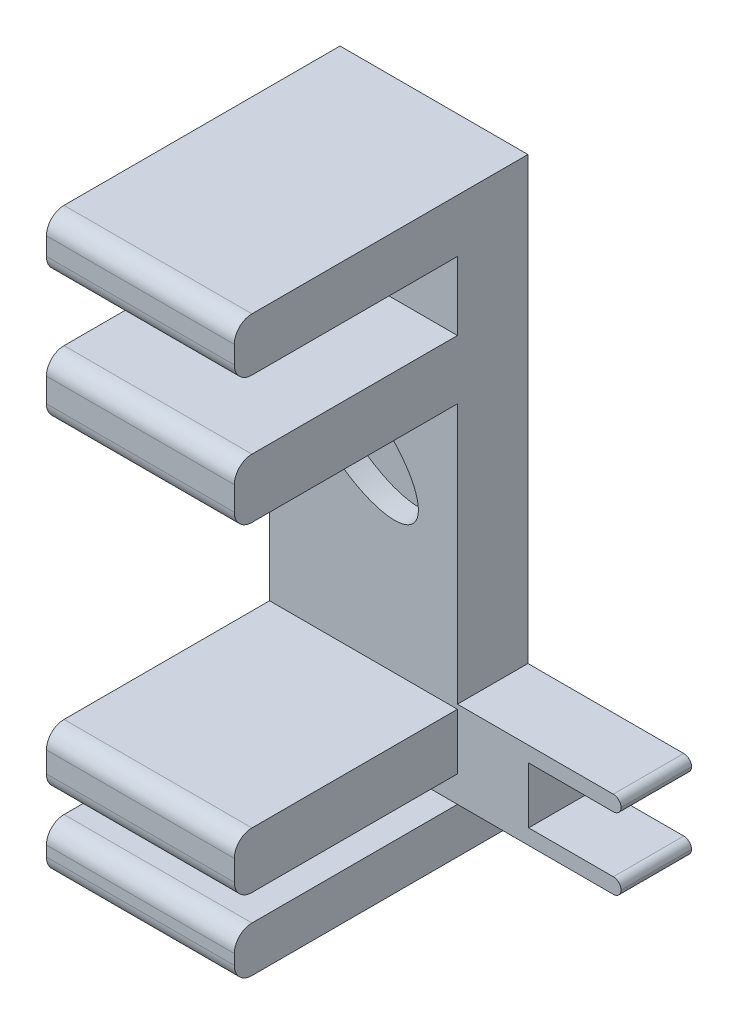
SolidWorks part; units mm, degrees
ref_plane "Front Plane" through (0, 0, 0) normal (0, 0, 1) x (1, 0, 0)
ref_plane "Top Plane" through (0, 0, 0) normal (0, 1, 0) x (1, 0, 0)
ref_plane "Right Plane" through (0, 0, 0) normal (1, 0, 0) x (0, 0, -1)
sketch "Sketch2" plane through (0, 0, 0) normal (0, 0, 1) x (1, 0, 0)
  line L0 (80, 56.32) -> (149.68, 56.32)
  line L1 (0, 0) -> (80, 0)
  line L2 (0, 0) -> (0, 244)
  line L3 (0, 244) -> (80, 244)
  line L4 (80, 0) -> (80, 56.32)
  line L5 (149.68, 56.32) -> (149.68, 49.83)
  line L6 (149.68, 49.83) -> (110.31, 49.83)
  line L7 (110.31, 49.83) -> (110.31, 25.8796)
  line L8 (110.31, 25.8796) -> (149.68, 25.8796)
  line L9 (149.68, 25.8796) -> (149.68, 19.3896)
  line L10 (149.68, 19.3896) -> (80, 19.3896)
  line L11 (80, 244) -> (80, 56.32)
  dimension "D1" = 244
  dimension "D2" = 80
  dimension "D3" = 187.68
  dimension "D4" = 69.68
  dimension "D6" = 6.49
  dimension "D7" = 6.49
  dimension "D8" = 39.37
extrude "Boss-Extrude2" add sketch "Sketch2" along normal mid plane 30 contours L11 L3 L2 L1 L4 | L10 L9 L8 L7 L6 L5 L0 L4 region at (106.0751, 37.8548, 0) region at (40, 122, 0)
fillet "Fillet1" radius 3.33 4 edges at (149.68, 19.3896, 0) (149.68, 25.8796, 0) (149.68, 49.83, 0) (149.68, 56.32, 0)
sketch "Sketch3" plane through (0, 0, 0) normal (0, 0, 1) x (1, 0, 0)
  line L0 (0, 244) -> (80, 244) construction
  line L1 (0, 221.4078) -> (80, 221.4078)
  line L2 (0, 0) -> (0, 244) construction
  line L3 (80, 244) -> (80, 56.32) construction
  line L4 (80, 221.4078) -> (0, 221.4078)
  line L5 (80, 221.4078) -> (80, 244)
  line L6 (80, 244) -> (0, 244)
  line L7 (0, 221.4078) -> (0, 244)
  line L13 (80, 19.3896) -> (146.35, 19.3896)
  line L14 (146.35, 25.8796) -> (110.31, 25.8796)
  line L15 (110.31, 25.8796) -> (110.31, 49.83)
  line L16 (110.31, 49.83) -> (146.35, 49.83)
  line L17 (146.35, 56.32) -> (80, 56.32)
  line L18 (80, 56.32) -> (80, 244)
  line L19 (80, 244) -> (0, 244)
  line L20 (0, 244) -> (0, 0)
  line L21 (0, 0) -> (80, 0)
  line L22 (80, 0) -> (80, 19.3896)
  line L23 (80, 19.3896) -> (146.35, 19.3896)
  line L24 (146.35, 25.8796) -> (110.31, 25.8796)
  line L25 (110.31, 25.8796) -> (110.31, 49.83)
  line L26 (110.31, 49.83) -> (146.35, 49.83)
  line L27 (146.35, 56.32) -> (80, 56.32)
  line L28 (80, 56.32) -> (80, 221.4078)
  line L30 (0, 221.4078) -> (0, 0)
  line L31 (0, 0) -> (80, 0)
  line L32 (80, 0) -> (80, 19.3896)
  arc A4 (146.35, 19.3896) -> (149.6789, 22.6346) centre (146.35, 22.7196) ccw
  arc A5 (149.6789, 22.6346) -> (146.35, 25.8796) centre (146.35, 22.5496) ccw
  arc A6 (146.35, 49.83) -> (149.6789, 53.075) centre (146.35, 53.16) ccw
  arc A7 (149.6789, 53.075) -> (146.35, 56.32) centre (146.35, 52.99) ccw
  arc A8 (146.35, 19.3896) -> (149.6789, 22.6346) centre (146.35, 22.7196) ccw
  arc A9 (149.6789, 22.6346) -> (146.35, 25.8796) centre (146.35, 22.5496) ccw
  arc A10 (146.35, 49.83) -> (149.6789, 53.075) centre (146.35, 53.16) ccw
  arc A11 (149.6789, 53.075) -> (146.35, 56.32) centre (146.35, 52.99) ccw
  dimension "D1" = 22.5922
  dimension "D2" = 0
extrude "Boss-Extrude3" add sketch "Sketch3" along normal blind 110 contours L7 L1 L5 L6 region at (40, 232.7039, 0)
sketch "Sketch4" plane through (0, 0, 0) normal (0, 0, 1) x (1, 0, 0)
  line L0 (0, 0) -> (0, 221.4078) construction
  line L1 (0, 167.0864) -> (80, 167.0864)
  line L2 (0, 167.0864) -> (0, 192.2667)
  line L3 (0, 192.2667) -> (80, 192.2667)
  line L4 (80, 167.0864) -> (80, 192.2667)
  line L5 (80, 221.4078) -> (80, 56.32) construction
  line L7 (0, 0) -> (80, 0)
  line L8 (0, 0) -> (0, 19.3896)
  line L9 (0, 19.3896) -> (80, 19.3896)
  line L10 (80, 0) -> (80, 19.3896)
  line L11 (0, 54.4555) -> (80, 54.4555)
  line L12 (0, 54.4555) -> (0, 30.6363)
  line L13 (0, 30.6363) -> (80, 30.6363)
  line L14 (80, 54.4555) -> (80, 30.6363)
extrude "Boss-Extrude4" add sketch "Sketch4" along normal blind 110
fillet "Fillet2" radius 7.5 8 edges at (40, 0, 110) (40, 19.3896, 110) (40, 30.6363, 110) (40, 54.4555, 110) (40, 167.0864, 110) (40, 192.2667, 110) (40, 221.4078, 110) (40, 244, 110)
sketch "Sketch5" plane through (0, 0, 15) normal (0, 0, 1) x (1, 0, 0)
  ellipse E0 centre (37.069, 133.7395) end of major axis (61.5687, 114.0035) minor radius 15.1854
extrude "Cut-Extrude1" cut sketch "Sketch5" against normal blind 10
